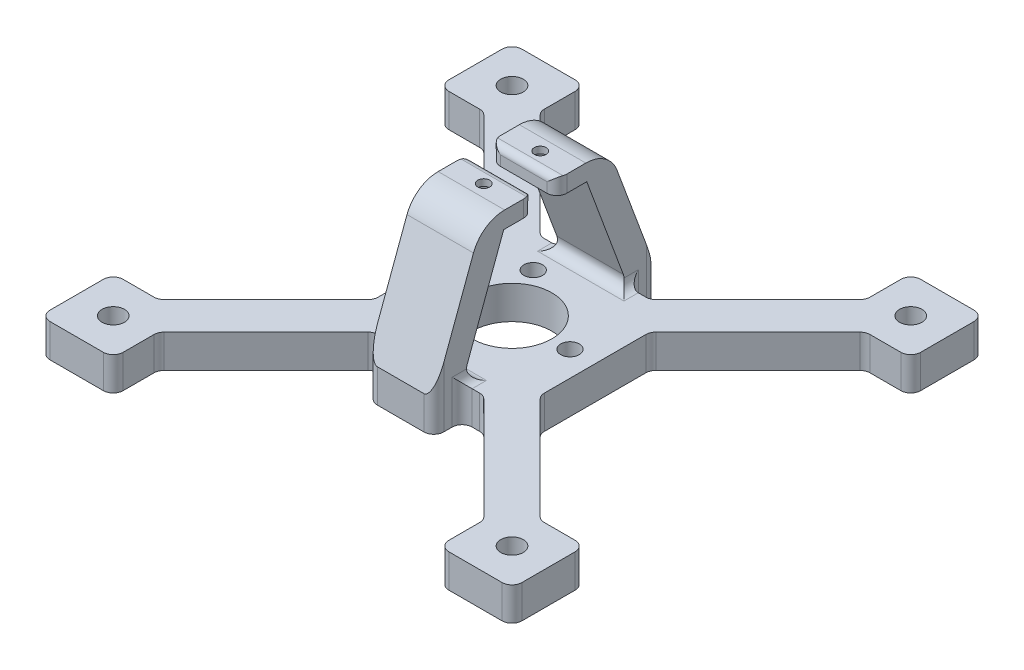
SolidWorks part; units mm, degrees
ref_plane "Front Plane" through (0, 0, 0) normal (0, 0, 1) x (1, 0, 0)
ref_plane "Top Plane" through (0, 0, 0) normal (0, 1, 0) x (1, 0, 0)
ref_plane "Right Plane" through (0, 0, 0) normal (1, 0, 0) x (0, 0, -1)
sketch "Sketch1" plane through (0, 0, 0) normal (0, 1, 0) x (1, 0, 0)
  line L0 (50, 75) -> (50, 50)
  line L1 (0, 0) -> (150, 0) construction
  line L2 (0, 0) -> (0, 150) construction
  line L3 (0, 150) -> (150, 150) construction
  line L4 (150, 0) -> (150, 150) construction
  line L5 (75, 150) -> (75, 0) construction
  line L6 (0, 75) -> (150, 75) construction
  line L7 (50, 50) -> (75, 50)
  line L8 (100, 50) -> (75, 50)
  line L9 (4, 4) -> (26, 4)
  line L10 (17.5147, 26) -> (50, 58.4853)
  line L11 (26, 17.5147) -> (58.4853, 50)
  line L12 (4, 4) -> (4, 26)
  line L13 (4, 26) -> (26, 26)
  line L14 (26, 4) -> (26, 26)
  line L15 (15, 26) -> (15, 4) construction
  line L16 (4, 15) -> (26, 15) construction
  line L17 (100, 100) -> (100, 50)
  line L18 (124, 17.5147) -> (91.5147, 50)
  line L19 (132.4853, 26) -> (100, 58.4853)
  line L20 (146, 26) -> (124, 26)
  line L21 (124, 4) -> (124, 26)
  line L22 (146, 4) -> (124, 4)
  line L23 (146, 4) -> (146, 26)
  line L24 (4, 135) -> (26, 135) construction
  line L25 (15, 124) -> (15, 146) construction
  line L26 (146, 146) -> (146, 124)
  line L27 (146, 146) -> (124, 146)
  line L28 (124, 146) -> (124, 124)
  line L29 (146, 124) -> (124, 124)
  line L30 (132.4853, 124) -> (100, 91.5147)
  line L31 (124, 132.4853) -> (91.5147, 100)
  line L32 (26, 146) -> (26, 124)
  line L33 (4, 124) -> (26, 124)
  line L34 (4, 146) -> (4, 124)
  line L35 (26, 132.4853) -> (58.4853, 100)
  line L36 (17.5147, 124) -> (50, 91.5147)
  line L37 (4, 146) -> (26, 146)
  line L38 (100, 100) -> (75, 100)
  line L39 (50, 100) -> (75, 100)
  line L40 (50, 75) -> (50, 100)
  line L41 (50, 50) -> (58.4853, 50) construction
  line L42 (50, 50) -> (50, 58.4853) construction
  line L43 (50, 58.4853) -> (58.4853, 50) construction
  point P4 (15, 15)
  point P5 (135, 15)
  point P6 (135, 135)
  point P7 (15, 135)
  point P12 (15, 15)
  point P47 (100, 75)
  point P444 (75, 75)
  dimension "D8" = 135
  dimension "D1" = 150
  dimension "D2" = 150
  dimension "D3" = 15
  dimension "D4" = 15
  dimension "D5" = 4
  dimension "D6" = 25
  dimension "D7" = 4
  dimension "D9" = 12
  dimension "D10" = 45
extrude "Boss-Extrude1" add sketch "Sketch1" against normal blind 10 contours L9 L14 L13 L12 | L14 L11 L7 L0 L10 L13 | L40 L0 L7 L8 L17 L38 L39 | L18 L21 L20 L19 L17 L8 | L22 L23 L20 L21 | L29 L26 L27 L28 | L38 L17 L30 L29 L28 L31 | L36 L40 L39 L35 L32 L33 | L37 L34 L33 L32
hole_wizard "1/4 Clearance Hole1" positions "Sketch2" profile "Sketch3" hole size "1/4" standard "ANSI Inch" end condition through all
sketch "Sketch2" plane through (0, 0, 0) normal (0, 1, 0) x (1, 0, 0)
  point P0 (15, 15)
  point P3 (15, 135)
  point P6 (135, 135)
  point P9 (135, 15)
sketch "Sketch3" plane through (15, 0, -15) normal (1, 0, 0) x (0, 0, 1)
  line L0 (0, 0) -> (0, 10)
  line L1 (0, 10) -> (3.3782, 10)
  line L2 (3.3782, 10) -> (3.3782, 0)
  line L5 (3.3782, 0) -> (0, 0)
  line L11 (0, -6.35) -> (0, 107.95) construction
  dimension "Thru Hole Dia." = 6.7564
  dimension "Thru Hole Depth" = 10
sketch "Sketch6" plane through (0, -10, 0) normal (0, -1, 0) x (1, 0, 0)
  line L0 (75, -100) -> (75, -50) construction
  line L1 (91.5147, -100) -> (58.4853, -100) construction
  line L2 (58.4853, -50) -> (91.5147, -50) construction
  circle A0 centre (75, -75) radius 4
  dimension "D1" = 8
extrude "Cut-Extrude1" cut sketch "Sketch6" against normal through all
sketch "Sketch7" plane through (0, -10, 0) normal (0, 1, 0) x (1, 0, 0)
  circle A0 centre (75, 75) radius 12
  dimension "D1" = 24
extrude "Cut-Extrude2" cut sketch "Sketch7" along normal through all
hole_wizard "CBORE for #10 Socket Head Cap Screw1" positions "Sketch8" profile "Sketch9" counterbore size "#10" standard "ANSI Inch" end condition through all
sketch "Sketch8" plane through (0, -10, 0) normal (0, -1, 0) x (-1, 0, 0)
  point P0 (-92.45, 75)
  point P3 (-66.275, 59.8879)
  point P6 (-66.275, 90.1121)
sketch "Sketch9" plane through (92.45, -10, -75) normal (1, 0, 0) x (0, 0, -1)
  line L0 (0, 0) -> (0, 10)
  line L1 (0, 10) -> (2.8067, 10)
  line L3 (2.8067, 10) -> (2.8067, 4.826)
  line L4 (2.8067, 4.826) -> (4.7625, 4.826)
  line L5 (4.7625, 4.826) -> (4.7625, 0)
  line L7 (4.7625, 0) -> (0, 0)
  line L11 (0, -6.35) -> (0, 107.95) construction
  dimension "Thru Hole Dia." = 5.6134
  dimension "Thru Hole Depth" = 10
  dimension "C'Bore Dia." = 9.525
  dimension "C'Bore Depth" = 4.826
ref_plane "Plane1" through (75, 0, 0) normal (-1, 0, 0) x (0, 0, 1)
sketch "Sketch10" plane through (75, 0, 0) normal (-1, 0, 0) x (0, 0, 1)
  line L0 (-100, -10) -> (-50, -10) construction
  line L1 (-75, -10) -> (-75, 27.8404) construction
  line L2 (-100, -10) -> (-100, 0)
  line L3 (-100, 0) -> (-87.5, 33.7044)
  line L5 (-87.5, 38.7044) -> (-62.5, 38.7044) construction
  line L6 (-87.5, 38.7044) -> (-94.1781, 38.7044)
  line L7 (-94.1781, 38.7044) -> (-108.5325, 0)
  line L8 (-132.4853, 0) -> (-100, 0) construction
  line L9 (-108.5325, 0) -> (-108.5325, -10)
  line L10 (-132.4853, -10) -> (-100, -10) construction
  line L11 (-108.5325, -10) -> (-100, -10)
  line L26 (-87.5, 33.7044) -> (-78.5, 33.7044)
  line L27 (-78.5, 33.7044) -> (-78.5, 38.7044)
  line L28 (-78.5, 38.7044) -> (-87.5, 38.7044)
  line L29 (-71.5, 33.7044) -> (-71.5, 38.7044)
  line L30 (-62.5, 33.7044) -> (-71.5, 33.7044)
  line L31 (-50, 0) -> (-62.5, 33.7044)
  line L32 (-50, -10) -> (-50, 0)
  line L33 (-41.4675, -10) -> (-50, -10)
  line L34 (-41.4675, 0) -> (-41.4675, -10)
  line L35 (-55.8219, 38.7044) -> (-41.4675, 0)
  line L36 (-62.5, 38.7044) -> (-55.8219, 38.7044)
  line L37 (-71.5, 38.7044) -> (-62.5, 38.7044)
  line L38 (-87.5, 43.0544) -> (-87.5, 38.7044) construction
  dimension "D1" = 5
  dimension "D2" = 8
extrude "Boss-Extrude2" add sketch "Sketch10" along normal blind 10 and the other way blind 10
hole_wizard "CBORE for M3 SHCS1" positions "Sketch11" profile "Sketch12" counterbore size "M3" standard "ANSI Metric" end condition through all
sketch "Sketch11" plane through (0, 33.7044, 0) normal (0, -1, 0) x (-1, 0, 0)
  point P0 (-75, 83.5)
  point P3 (-75, 66.5)
sketch "Sketch12" plane through (75, 33.7044, -83.5) normal (1, 0, 0) x (0, 0, -1)
  line L0 (0, 0) -> (0, 5)
  line L1 (0, 5) -> (1.8, 5)
  line L3 (1.8, 5) -> (1.8, 3)
  line L4 (1.8, 3) -> (3.25, 3)
  line L5 (3.25, 3) -> (3.25, 0)
  line L7 (3.25, 0) -> (0, 0)
  line L11 (0, -6.35) -> (0, 107.95) construction
  dimension "Thru Hole Dia." = 3.6
  dimension "Thru Hole Depth" = 5
  dimension "C'Bore Dia." = 6.5
  dimension "C'Bore Depth" = 3
fillet "Fillet1" radius 3 40 edges at (65, 36.2044, -71.5) (85, 36.2044, -71.5) (85, 36.2044, -78.5) (65, 36.2044, -78.5) (50, -5, -58.4853) (50, -5, -91.5147) (17.5147, -5, -124) (4, -5, -124) (4, -5, -146) (26, -5, -146) (26, -5, -132.4853) (58.4853, -5, -100) (65, -5, -100) (65, -5, -108.5325) (85, -5, -108.5325) (85, -5, -100) (91.5147, -5, -100) (124, -5, -132.4853) (124, -5, -146) (146, -5, -146) (146, -5, -124) (132.4853, -5, -124) (100, -5, -91.5147) (100, -5, -58.4853) (132.4853, -5, -26) (146, -5, -26) (146, -5, -4) (124, -5, -4) (124, -5, -17.5147) (91.5147, -5, -50) (85, -5, -41.4675) (85, -5, -50) (65, -5, -41.4675) (65, -5, -50) (58.4853, -5, -50) (17.5147, -5, -26) (26, -5, -4) (26, -5, -17.5147) (4, -5, -26) (4, -5, -4)
fillet "Fillet2" radius 3 6 edges at (85, 0, -48.5) (85, 0, -101.5) (65, 0, -48.5) (65, 0, -101.5) (75, 0, -50) (75, 0, -100)
fillet "Fillet3" radius 10 2 edges at (75, 38.7044, -94.1781) (75, 38.7044, -55.8219)
fillet "Fillet4" radius 2 2 edges at (75, 38.7044, -71.5) (75, 38.7044, -78.5)
